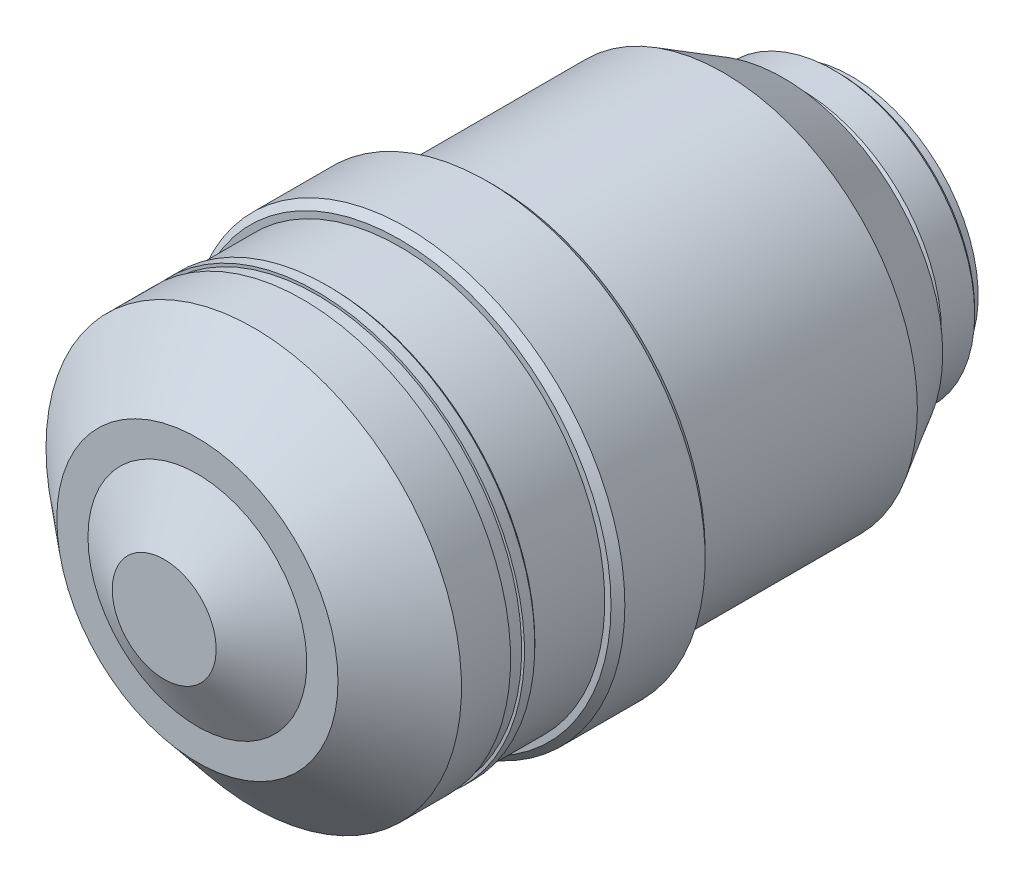
SolidWorks part; units mm, degrees
ref_plane "Front Plane" through (0, 0, 0) normal (0, 0, 1) x (1, 0, 0)
ref_plane "Top Plane" through (0, 0, 0) normal (0, 1, 0) x (1, 0, 0)
ref_plane "Right Plane" through (0, 0, 0) normal (1, 0, 0) x (0, 0, -1)
sketch "Sketch1" plane through (0, 0, 0) normal (0, 1, 0) x (1, 0, 0)
  line L0 (0, 0) -> (-3.75, 0) construction
  line L1 (0, 0) -> (0, 49.96) construction
  line L2 (0, 0.17) -> (-3.75, 0.17) construction
  line L3 (0, 0.35) -> (-3.75, 0.35)
  line L4 (-3.75, 0.35) -> (-7.9, 2.746)
  line L5 (-7.9, 2.746) -> (-10.15, 2.746)
  line L6 (-10.15, 2.746) -> (-15, 6.8156)
  line L7 (-15, 6.8156) -> (-15, 10.36)
  line L8 (0, 49.96) -> (-9.16, 49.96)
  line L9 (-9.16, 49.96) -> (-9.16, 48.96)
  line L10 (-9.16, 48.96) -> (-10.16, 48.96)
  line L11 (-10.16, 48.96) -> (-10.16, 46.06)
  line L12 (-10.16, 46.06) -> (-9.16, 46.06)
  line L13 (-9.16, 46.06) -> (-9.16, 45.06)
  line L14 (-9.16, 45.06) -> (-11.5, 45.06)
  line L15 (-11.5, 45.06) -> (-14, 40.7299)
  line L16 (-14, 40.7299) -> (-14, 24.16)
  line L17 (-14, 24.16) -> (-15.75, 24.16)
  line L18 (-15.75, 24.16) -> (-15.75, 17.36)
  line L19 (-15.75, 17.36) -> (-14.8, 17.36)
  line L20 (-14.8, 17.36) -> (-14.8, 12.36)
  line L21 (-14.8, 12.36) -> (-15, 12.36)
  line L22 (-15, 12.36) -> (-15, 11.36)
  line L23 (-15, 11.36) -> (-14.8, 11.36)
  line L24 (-14.8, 11.36) -> (-14.8, 10.36)
  line L25 (-14.8, 10.36) -> (-15, 10.36)
  line L26 (0, 49.96) -> (0, 0.35)
  dimension "D1" = 3.75
  dimension "D2" = 14
  dimension "D3" = 0.17
  dimension "D4" = 0.18
  dimension "D5" = 7.9
  dimension "D6" = 15.75
  dimension "D7" = 4.9
  dimension "D8" = 1
  dimension "D9" = 1
  dimension "D10" = 10.16
  dimension "D11" = 1
  dimension "D12" = 44.71
  dimension "D13" = 30
  dimension "D14" = 11.5
  dimension "D15" = 20.9
  dimension "D16" = 27.7
  dimension "D17" = 14.8
  dimension "D18" = 15
  dimension "D19" = 10.15
  dimension "D20" = 40
  dimension "D21" = 30
  dimension "D22" = 1
  dimension "D23" = 1
  dimension "D24" = 5
revolve "Revolve1" add sketch "Sketch1" angle 360 about L26
chamfer "Chamfer1" distance 0.25 angle 45 3 edges at (-15, 0, -12.36) (-10.16, 0, -48.96) (-10.16, 0, -46.06)
chamfer "Chamfer2" distance 0.5 angle 45 2 edges at (-15.75, 0, -24.16) (-15.75, 0, -17.36)
sketch "Sketch2" plane through (0, 0, -49.96) normal (0, 0, -1) x (-1, 0, 0)
  circle A0 centre (0, 0) radius 4.275
  dimension "D1" = 8.55
extrude "Cut-Extrude1" cut sketch "Sketch2" against normal blind 1
